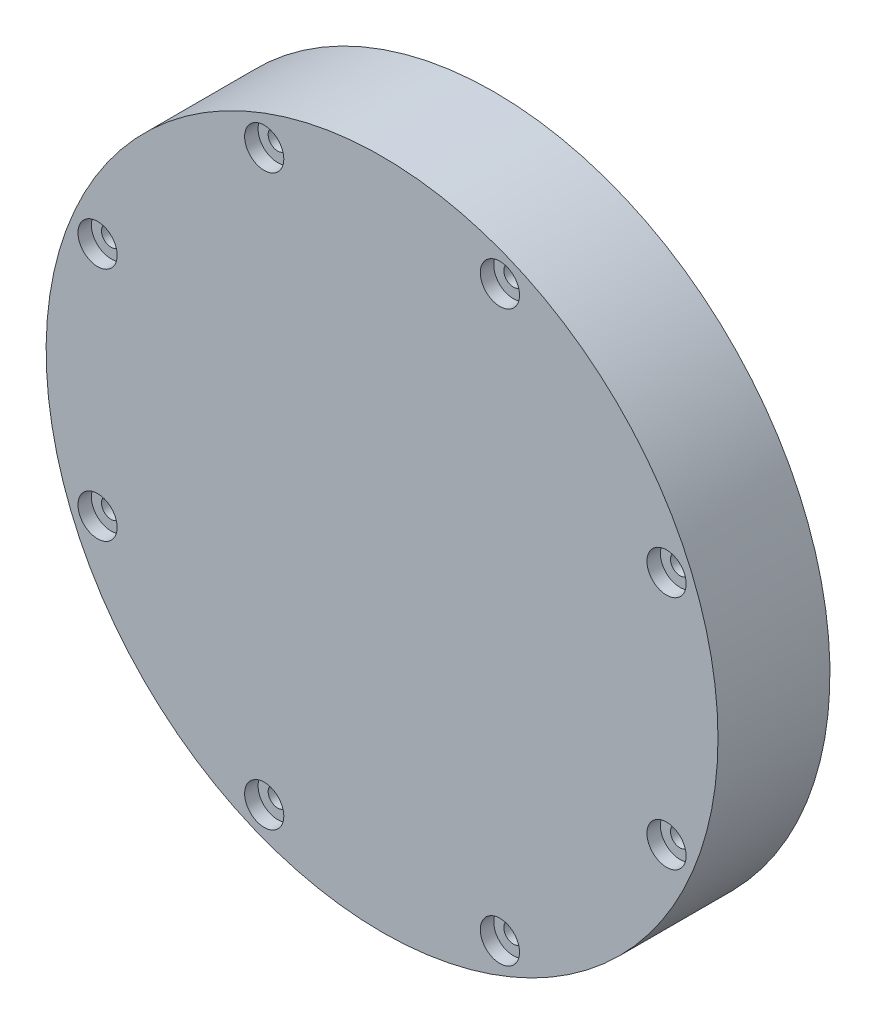
SolidWorks part; units mm, degrees
material "ABS"
ref_plane "Front" through (0, 0, 0) normal (0, 0, 1) x (1, 0, 0)
ref_plane "Top" through (0, 0, 0) normal (0, 1, 0) x (1, 0, 0)
ref_plane "Right" through (0, 0, 0) normal (1, 0, 0) x (0, 0, -1)
sketch "Croquis1" plane through (0, 0, 0) normal (0, 0, 1) x (1, 0, 0)
  line L0 (-15, -49.8498) -> (-15, -54.0833)
  line L1 (15, -49.8498) -> (15, -54.0833)
  line L2 (-15, -47.697) -> (15, -47.697) construction
  line L3 (0, -50) -> (0, 50) construction
  arc A0 (18.9474, -56.9298) -> (-18.9474, -56.9298) centre (0, 0) ccw
  arc A1 (16.9811, -47.0281) -> (-16.9811, -47.0281) centre (0, 0) ccw
  arc A2 (15, -54.0833) -> (18.9474, -56.9298) centre (18, -54.0833) ccw
  arc A3 (-15, -54.0833) -> (-18.9474, -56.9298) centre (-18, -54.0833) cw
  arc A4 (15, -49.8498) -> (16.9811, -47.0281) centre (18, -49.8498) cw
  arc A5 (-15, -49.8498) -> (-16.9811, -47.0281) centre (-18, -49.8498) ccw
  point P8 (0, -47.697)
  dimension "D1" = 120
  dimension "D2" = 100
  dimension "D4" = 3
  dimension "D3" = 30
extrude "Saliente-Extruir1" add sketch "Croquis1" along normal blind 15
sketch "Croquis2" plane through (0, 0, 15) normal (0, 0, 1) x (1, 0, 0)
  circle A0 centre (0, 0) radius 60
  dimension "D1" = 120
extrude "Saliente-Extruir2" add sketch "Croquis2" along normal blind 5
hole_wizard "Refrentado para tornillo con cabeza troncocónica de M31" positions "Croquis3" profile "Croquis5" counterbore size "M3" standard "Ansi Metric" end condition up to next
sketch "Croquis3" plane through (0, 0, 20) normal (0, 0, 1) x (1, 0, 0)
  line L1 (-21.0476, -50.8134) -> (21.0476, 50.8134) construction
  line L4 (0, -50) -> (0, 50) construction
  point P4 (21.0476, 50.8134)
  point P18 (50.8134, 21.0476)
  point P19 (50.8134, -21.0476)
  point P20 (21.0476, -50.8134)
  point P21 (-21.0476, -50.8134)
  point P22 (-50.8134, -21.0476)
  point P23 (-50.8134, 21.0476)
  point P24 (-21.0476, 50.8134)
  dimension "D1" = 22.5
  dimension "D2" = 110
  dimension "D3" = 8
sketch "Croquis5" plane through (-21.0476, 50.8134, 20) normal (1, 0, 0) x (0, -1, 0)
  line L0 (0, 0) -> (0, 20)
  line L1 (0, 20) -> (1.7, 20)
  line L3 (1.7, 20) -> (1.7, 2.4)
  line L4 (1.7, 2.4) -> (3.5, 2.4)
  line L5 (3.5, 2.4) -> (3.5, 0)
  line L7 (3.5, 0) -> (0, 0)
  line L11 (0, -6.35) -> (0, 107.95) construction
  dimension "Diámetro de taladro hasta el siguiente" = 3.4
  dimension "Profundidad de taladro hasta el siguiente" = 20
  dimension "Diámetro de refrentado" = 7
  dimension "Profundidad de refrentado" = 2.4
sketch "Croquis6" plane through (0, 0, 0) normal (1, 0, 0) x (0, 0, -1)
  line L0 (147, 19.1127) -> (147, 0) construction
  line L1 (50, 0) -> (-50, 0) construction
  line L2 (147, 0) -> (127.8873, 0) construction
  line L3 (-20, 60) -> (-20, -60) construction
  point P4 (46.846, 21.3563)
  point P9 (127.8873, 0)
  dimension "D1" = 167
